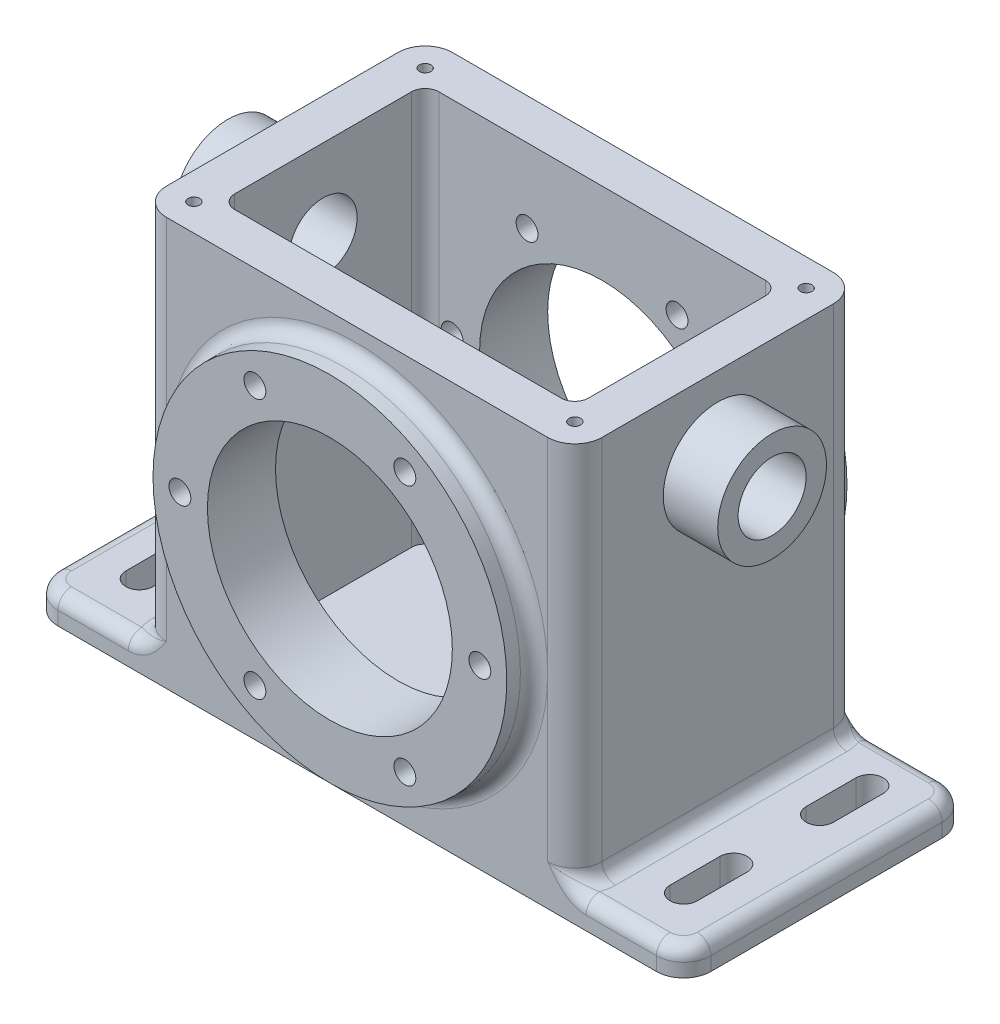
SolidWorks part; units mm, degrees
material "Cast Alloy Steel"
ref_plane "Front Plane" through (0, 0, 0) normal (0, 0, 1) x (1, 0, 0)
ref_plane "Top Plane" through (0, 0, 0) normal (0, 1, 0) x (1, 0, 0)
ref_plane "Right Plane" through (0, 0, 0) normal (1, 0, 0) x (0, 0, -1)
sketch "Sketch1" plane through (0, 0, 0) normal (0, 1, 0) x (1, 0, 0)
  line L0 (-76.2, 33.3375) -> (76.2, -33.3375) construction
  line L1 (-76.2, 33.3375) -> (76.2, 33.3375)
  line L2 (-76.2, 33.3375) -> (-76.2, -33.3375)
  line L3 (-76.2, -33.3375) -> (76.2, -33.3375)
  line L4 (76.2, 33.3375) -> (76.2, -33.3375)
  dimension "D1" = 66.675
  dimension "D2" = 152.4
extrude "Boss-Extrude1" add sketch "Sketch1" along normal blind 6.35
sketch "Sketch2" plane through (0, 6.35, 0) normal (0, 1, 0) x (1, 0, 0)
  line L0 (76.2, 33.3375) -> (-76.2, 33.3375) construction
  line L1 (-50.8, -33.3375) -> (50.8, -33.3375)
  line L2 (-50.8, -33.3375) -> (-50.8, 33.3375)
  line L3 (-50.8, 33.3375) -> (50.8, 33.3375)
  line L4 (50.8, -33.3375) -> (50.8, 33.3375)
  line L5 (-50.8, -33.3375) -> (50.8, 33.3375) construction
  line L6 (-50.8, 33.3375) -> (50.8, -33.3375) construction
  point P0 (0, 0)
  dimension "D1" = 101.6
extrude "Boss-Extrude3" add sketch "Sketch2" along normal blind 88.9
fillet "Fillet4" radius 6.35 8 edges at (-76.2, 3.175, -33.3375) (-76.2, 3.175, 33.3375) (76.2, 3.175, -33.3375) (76.2, 3.175, 33.3375)
fillet "Fillet5" radius 3.175 16 edges at (-74.3401, 6.35, -31.4776) (-74.3401, 6.35, 31.4776) (-48.9401, 6.35, -31.4776) (-48.9401, 6.35, 31.4776) (74.3401, 6.35, -31.4776) (76.2, 6.35, 0) (74.3401, 6.35, 31.4776) (48.9401, 6.35, 31.4776) (48.9401, 6.35, -31.4776) (-76.2, 6.35, 0)
sketch "Sketch4" plane through (0, 95.25, 0) normal (0, 1, 0) x (1, 0, 0)
  line L0 (44.45, 33.3375) -> (-44.45, 33.3375) construction
  line L1 (-41.275, 23.8125) -> (41.275, 23.8125)
  line L2 (-41.275, 23.8125) -> (-41.275, -23.8125)
  line L3 (-41.275, -23.8125) -> (41.275, -23.8125)
  line L4 (41.275, 23.8125) -> (41.275, -23.8125)
  line L5 (-44.45, -33.3375) -> (44.45, -33.3375) construction
  line L6 (50.8, -26.9875) -> (50.8, 26.9875) construction
  line L7 (-50.8, 26.9875) -> (-50.8, -26.9875) construction
  dimension "D1" = 9.525
  dimension "D2" = 9.525
  dimension "D3" = 9.525
  dimension "D4" = 9.525
extrude "Cut-Extrude1" cut sketch "Sketch4" against normal blind 92.075
fillet "Fillet6" radius 3.175 4 edges at (41.275, 49.2125, 23.8125) (-41.275, 49.2125, 23.8125) (41.275, 49.2125, -23.8125) (-41.275, 49.2125, -23.8125)
sketch "Sketch5" plane through (0, 0, 33.3375) normal (0, 0, 1) x (1, 0, 0)
  line L0 (-44.45, 95.25) -> (44.45, 95.25) construction
  circle A0 centre (0, 47.625) radius 41.275
  dimension "D2" = 82.55
  dimension "D1" = 47.625
extrude "Boss-Extrude4" add sketch "Sketch5" along normal blind 6.3622
mirror "Mirror1" about plane through (0, 0, 0) normal (0, 0, 1) of "Boss-Extrude4"
sketch "Sketch6" plane through (50.8, 0, 0) normal (1, 0, 0) x (0, 0, -1)
  line L0 (-26.9875, 95.25) -> (26.9875, 95.25) construction
  circle A0 centre (0, 76.2) radius 12.7
  dimension "D2" = 25.4
  dimension "D1" = 19.05
extrude "Boss-Extrude5" add sketch "Sketch6" along normal blind 12.7
mirror "Mirror2" about plane through (0, 0, 0) normal (1, 0, 0) of "Boss-Extrude5"
sketch "Sketch7" plane through (-63.5, 0, 0) normal (-1, 0, 0) x (0, 0, 1)
  circle A0 centre (0, 76.2) radius 7.9375
  dimension "D1" = 15.875
extrude "Cut-Extrude2" cut sketch "Sketch7" against normal through all
sketch "Sketch8" plane through (0, 0, 39.6997) normal (0, 0, 1) x (1, 0, 0)
  circle A0 centre (0, 47.625) radius 28.575
  dimension "D1" = 57.15
extrude "Cut-Extrude3" cut sketch "Sketch8" against normal through all
sketch "Sketch14" plane through (0, 0, -39.6997) normal (0, 0, -1) x (-1, 0, 0)
  line L1 (41.275, 47.625) -> (0, 47.625) construction
  circle A0 centre (0, 47.625) radius 41.275 construction
hole_wizard "1/4-20 Tapped Hole1" positions "Sketch16" profile "Sketch15" tap size "1/4-20" standard "ANSI Inch" end condition up to next
sketch "Sketch16" plane through (0, 0, -39.6997) normal (0, 0, -1) x (-1, 0, 0)
  line L0 (41.275, 47.625) -> (0, 47.625) construction
  point P0 (34.9983, 47.625)
sketch "Sketch15" plane through (-34.9983, 47.625, -39.6997) normal (1, 0, 0) x (0, 1, 0)
  line L0 (0, 0) -> (0, 15.8882)
  line L1 (0, 15.8882) -> (2.5527, 15.8882)
  line L2 (2.5527, 15.8882) -> (2.5527, 0)
  line L5 (2.5527, 0) -> (0, 0)
  line L11 (0, -6.35) -> (0, 107.95) construction
  dimension "Thru Tap Drill Dia." = 5.1054
  dimension "Thru Tap Drill Depth" = 15.8882
cosmetic thread "Hole Thread1" parameters "D2"=6.35
pattern_circular "CirPattern2" count 6 over 360 about axis through (0, 47.625, -39.6997) along (0, 0, 1) of "1/4-20 Tapped Hole1"
mirror "Mirror3" about plane through (0, 0, 0) normal (0, 0, 1) of "CirPattern2"
hole_wizard "#6-32 Tapped Hole1" positions "Sketch20" profile "Sketch19" tap size "#6-32" standard "ANSI Inch" end condition up to next
sketch "Sketch20" plane through (0, 95.25, 0) normal (0, 1, 0) x (1, 0, 0)
  point P0 (-44.45, -26.9875)
  point P3 (-44.45, 26.9875)
  point P6 (44.45, 26.9875)
  point P9 (44.45, -26.9875)
sketch "Sketch19" plane through (-44.45, 95.25, 26.9875) normal (1, 0, 0) x (0, 0, 1)
  line L0 (0, 0) -> (0, 95.25)
  line L1 (0, 95.25) -> (1.3525, 95.25)
  line L2 (1.3525, 95.25) -> (1.3525, 0)
  line L5 (1.3525, 0) -> (0, 0)
  line L11 (0, -6.35) -> (0, 107.95) construction
  dimension "Thru Tap Drill Dia." = 2.7051
  dimension "Thru Tap Drill Depth" = 95.25
cosmetic thread "Hole Thread2" parameters "D2"=3.5052
cosmetic thread "Hole Thread3" parameters "D2"=3.5052
cosmetic thread "Hole Thread4" parameters "D2"=3.5052
cosmetic thread "Hole Thread5" parameters "D2"=3.5052
sketch "Sketch21" plane through (0, 6.35, 0) normal (0, 1, 0) x (1, 0, 0)
  line L0 (-63.5, -20.6375) -> (-63.5, -9.0006) construction
  line L1 (-66.675, -20.6375) -> (-66.675, -9.0006)
  line L2 (-60.325, -20.6375) -> (-60.325, -9.0006)
  line L5 (-76.2, -26.9875) -> (-76.2, 26.9875) construction
  line L6 (-53.4303, -33.3375) -> (-69.85, -33.3375) construction
  arc A0 (-66.675, -20.6375) -> (-60.325, -20.6375) centre (-63.5, -20.6375) ccw
  arc A1 (-60.325, -9.0006) -> (-66.675, -9.0006) centre (-63.5, -9.0006) ccw
  point P2 (-63.5, -14.819)
  dimension "D1" = 6.35
  dimension "D2" = 12.7
  dimension "D3" = 12.7
extrude "Cut-Extrude5" cut sketch "Sketch21" against normal blind 10.16
pattern_linear "LPattern1" count 2 spacing 31.75 along (0, 0, -1) of "Cut-Extrude5"
mirror "Mirror4" about plane through (0, 0, 0) normal (1, 0, 0) of "LPattern1"
fillet "Fillet7" radius 3.175 2 edges at (41.275, 47.625, -33.3375) (-41.275, 47.625, 33.3375)
